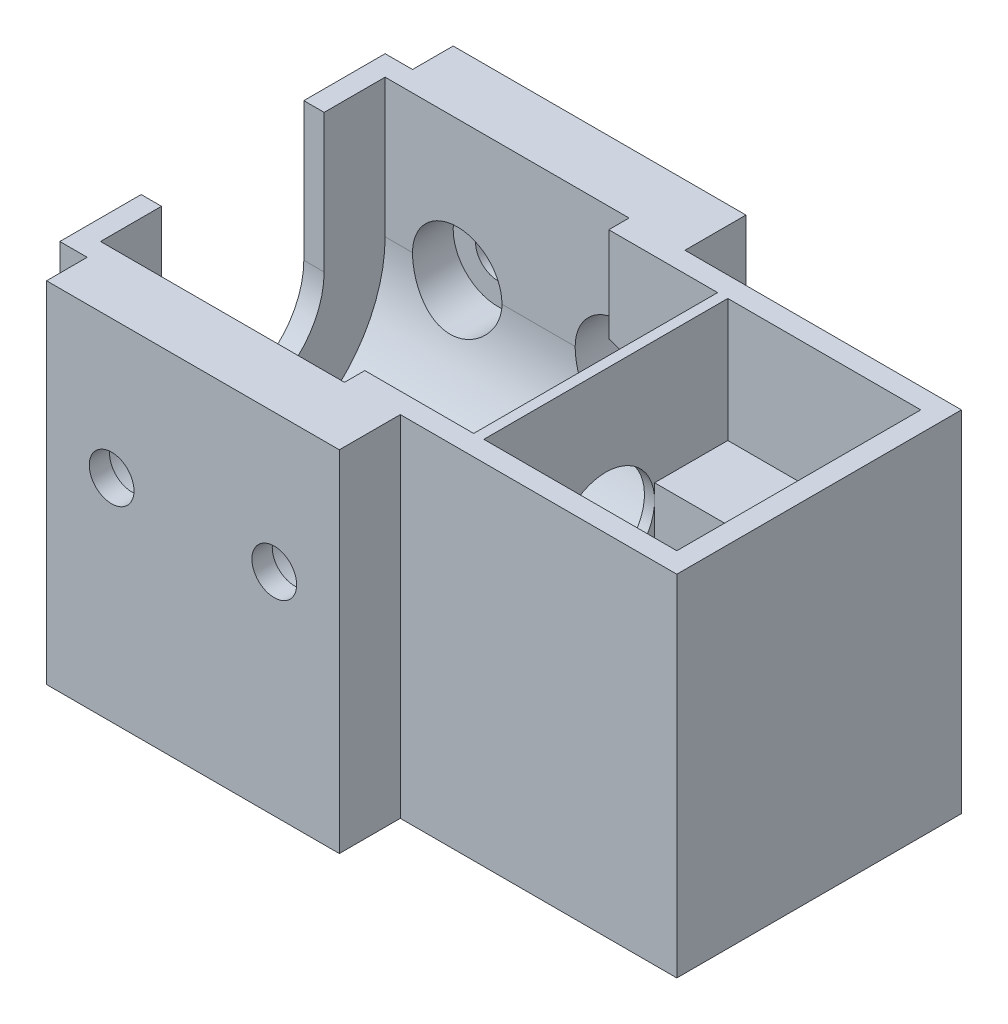
SolidWorks part; units mm, degrees
ref_plane "Front Plane" through (0, 0, 0) normal (0, 0, 1) x (1, 0, 0)
ref_plane "Top Plane" through (0, 0, 0) normal (0, 1, 0) x (1, 0, 0)
ref_plane "Right Plane" through (0, 0, 0) normal (1, 0, 0) x (0, 0, -1)
sketch "Sketch1" plane through (0, 0, 0) normal (0, 0, 1) x (1, 0, 0)
  line L1 (-76.2, -50.8) -> (40.64, -50.8)
  line L2 (-76.2, -50.8) -> (-76.2, 0)
  line L3 (-76.2, 0) -> (40.64, 0)
  line L4 (40.64, -50.8) -> (40.64, 0)
  line L5 (-76.2, -50.8) -> (40.64, 0) construction
  line L6 (-76.2, 0) -> (40.64, -50.8) construction
  point P0 (0, 0)
  dimension "D1" = 116.84
  dimension "D2" = 50.8
  dimension "D3" = 76.2
extrude "Boss-Extrude1" add sketch "Sketch1" along normal mid plane 63.5
sketch "Sketch2" plane through (0, 0, 0) normal (0, 0, 1) x (1, 0, 0)
  line L0 (-152.4829, -25.4) -> (6.8382, -25.4) construction
  line L1 (-49.3609, -3.175) -> (-49.3609, -12.7)
  line L2 (40.64, 0) -> (-76.2, 0) construction
  line L3 (40.64, 0) -> (-76.2, 0) construction
  line L4 (-11.2609, -3.175) -> (-11.2609, -6.35)
  line L5 (-11.2609, -25.4) -> (-11.2609, -3.175) construction
  line L6 (-128.4172, -25.4) -> (-157.8092, -25.4)
  line L7 (6.8382, -25.4) -> (40.64, -25.4)
  line L8 (-607.3619, -25.4) -> (6.8382, -25.4) construction
  line L9 (-49.3609, -3.175) -> (-11.2609, -3.175)
  line L10 (6.8382, -25.4) -> (-128.4172, -25.4)
  line L11 (-11.2609, -6.35) -> (5.7391, -6.35)
  line L12 (5.7391, -6.35) -> (5.7391, -17.78)
  line L13 (5.7391, -17.78) -> (23.7391, -17.78)
  line L14 (-49.3609, -12.7) -> (-220.2024, -12.7)
  line L15 (-220.2024, -12.7) -> (-220.2024, -25.4)
  line L16 (-220.2024, -25.4) -> (-157.8092, -25.4)
  line L17 (23.7391, -17.78) -> (23.7391, -25.4) construction
  line L18 (23.7391, -17.78) -> (40.64, -17.78)
  line L19 (40.64, -50.8) -> (40.64, 0) construction
  line L20 (40.64, -17.78) -> (40.64, -25.4)
  line L21 (-76.2, 0) -> (-76.2, -50.8) construction
  point P23 (-11.2609, -25.4)
  dimension "D1" = 22.225
  dimension "D2" = 38.1
  dimension "D3" = 25.4
  dimension "D4" = 35
  dimension "D5" = 7.62
  dimension "D6" = 3.175
  dimension "D7" = 26.8391
  dimension "D8" = 18
  dimension "D9" = 12.7
revolve "Cut-Revolve1" cut sketch "Sketch2" angle 360 about L0
sketch "Sketch38" plane through (40.64, 0, 0) normal (1, 0, 0) x (0, 0, -1)
  line L1 (-10, -35.4) -> (10, -35.4)
  line L2 (-10, -35.4) -> (-10, -15.4)
  line L3 (-10, -15.4) -> (10, -15.4)
  line L4 (10, -35.4) -> (10, -15.4)
  line L5 (-10, -35.4) -> (10, -15.4) construction
  line L6 (-10, -15.4) -> (10, -35.4) construction
  point P0 (0, -25.4)
  point P1 (0, -25.4)
  dimension "D1" = 20
  dimension "D2" = 20
extrude "Cut-Extrude33" cut sketch "Sketch38" against normal offset from surface (33.3134 mm away) 1.5875 up to face at (5.7391, -44.45, 0)
sketch "Sketch37" plane through (40.64, 0, 0) normal (1, 0, 0) x (0, 0, -1)
  line L0 (31.75, -50.8) -> (31.75, 0) construction
  line L1 (-31.75, 0) -> (31.75, 0)
  line L2 (-31.75, 0) -> (-31.75, -25.4)
  line L3 (-31.75, -25.4) -> (31.75, -25.4)
  line L4 (31.75, 0) -> (31.75, -25.4)
  line L5 (10, -35.4) -> (10, -15.4) construction
  point P7 (0, -25.4)
  point P11 (0, 0)
  point P14 (10, -25.4)
extrude "Cut-Extrude32" cut sketch "Sketch37" against normal through all
sketch "Sketch39" plane through (0, -25.4, 0) normal (0, 1, 0) x (1, 0, 0)
  line L10 (-76.2, 12.7) -> (-49.3609, 12.7)
  line L11 (-49.3609, 12.7) -> (-49.3609, 22.225)
  line L12 (-49.3609, 22.225) -> (-11.2609, 22.225)
  line L13 (-11.2609, 22.225) -> (-11.2609, 19.05)
  line L14 (-11.2609, 19.05) -> (5.7391, 19.05)
  line L15 (5.7391, 19.05) -> (5.7391, 7.62)
  line L16 (5.7391, 19.05) -> (5.7391, 7.62)
  line L17 (40.64, 10) -> (40.64, 31.75)
  line L18 (40.64, 31.75) -> (-76.2, 31.75)
  line L19 (-76.2, 31.75) -> (-76.2, 12.7)
  line L20 (-76.2, 12.7) -> (-49.3609, 12.7)
  line L21 (-49.3609, 12.7) -> (-49.3609, 22.225)
  line L22 (-49.3609, 22.225) -> (-11.2609, 22.225)
  line L23 (-11.2609, 22.225) -> (-11.2609, 19.05)
  line L24 (-11.2609, 19.05) -> (5.7391, 19.05)
  line L25 (7.3266, 10) -> (40.64, 10)
  line L26 (7.3266, 10) -> (40.64, 10)
  line L27 (40.64, 10) -> (40.64, 31.75)
  line L28 (40.64, 31.75) -> (-76.2, 31.75)
  line L29 (-76.2, 31.75) -> (-76.2, 12.7)
  line L30 (-49.3609, -12.7) -> (-76.2, -12.7)
  line L31 (-76.2, -12.7) -> (-76.2, -31.75)
  line L32 (-76.2, -31.75) -> (40.64, -31.75)
  line L33 (40.64, -31.75) -> (40.64, -10)
  line L34 (40.64, -10) -> (7.3266, -10)
  line L35 (40.64, -10) -> (7.3266, -10)
  line L36 (5.7391, -19.05) -> (-11.2609, -19.05)
  line L37 (-11.2609, -19.05) -> (-11.2609, -22.225)
  line L38 (-11.2609, -22.225) -> (-49.3609, -22.225)
  line L39 (-49.3609, -22.225) -> (-49.3609, -12.7)
  line L40 (-49.3609, -12.7) -> (-76.2, -12.7)
  line L41 (-76.2, -12.7) -> (-76.2, -31.75)
  line L42 (-76.2, -31.75) -> (40.64, -31.75)
  line L43 (40.64, -31.75) -> (40.64, -10)
  line L44 (5.7391, -7.62) -> (5.7391, -19.05)
  line L45 (5.7391, -7.62) -> (5.7391, -19.05)
  line L46 (5.7391, -19.05) -> (-11.2609, -19.05)
  line L47 (-11.2609, -19.05) -> (-11.2609, -22.225)
  line L48 (-11.2609, -22.225) -> (-49.3609, -22.225)
  line L49 (-49.3609, -22.225) -> (-49.3609, -12.7)
  line L52 (5.7391, 7.62) -> (7.3266, 7.62)
  line L53 (5.7391, 7.62) -> (7.3266, 7.62)
  line L54 (7.3266, 7.62) -> (7.3266, 10)
  line L55 (7.3266, 7.62) -> (7.3266, 10)
  line L56 (7.3266, -10) -> (7.3266, -7.62)
  line L57 (7.3266, -10) -> (7.3266, -7.62)
  line L58 (7.3266, -7.62) -> (5.7391, -7.62)
  line L59 (7.3266, -7.62) -> (5.7391, -7.62)
  dimension "D1" = 0
  dimension "D2" = 0
extrude "Boss-Extrude5" add sketch "Sketch39" along normal blind 25.4
sketch "Sketch40" plane through (0, 0, 0) normal (0, 1, 0) x (1, 0, 0)
  line L0 (7.3266, 10) -> (40.64, 10) construction
  line L1 (23.7391, 10) -> (40.64, 10)
  line L2 (23.7391, 10) -> (23.7391, -10)
  line L3 (23.7391, -10) -> (40.64, -10)
  line L4 (40.64, 10) -> (40.64, -10)
  line L6 (-11.2609, 22.225) -> (-11.2609, 19.05) construction
  dimension "D1" = 35
extrude "Boss-Extrude6" add sketch "Sketch40" against normal up to next
sketch "Sketch41" plane through (0, 0, 0) normal (0, 1, 0) x (1, 0, 0)
  line L2 (-76.2, 12.7) -> (-76.2, -12.7) construction
  circle A0 centre (-57.15, 0) radius 3.1134
  circle A1 centre (-31.75, 0) radius 3.1134
  circle A2 centre (-6.35, 0) radius 3.1134
  dimension "D1" = 19.05
extrude "Cut-Extrude34" cut sketch "Sketch41" against normal through all
ref_plane "Plane_Mid" through (0, -25.4, 0) normal (0, 1, 0) x (1, 0, 0)
ref_axis "Axis1" through (7.3266, -25.4, 0) along (-1, 0, 0)
sketch "Sketch42" plane through (0, 0, 0) normal (0, 0, 1) x (1, 0, 0)
  line L0 (1.7462, -25.4) -> (-1.7462, -25.4) construction
  line L1 (-76.2, 0) -> (-76.2, -25.4) construction
  circle A0 centre (-38.1, -25.4) radius 3.4925
  circle A1 centre (-12.7, -25.4) radius 3.4925
  dimension "D1" = 6.985
  dimension "D2" = 38.1
extrude "Cut-Extrude35" cut sketch "Sketch42" against normal through all both and the other way through all
sketch "Sketch43" plane through (0, 0, 0) normal (0, 0, 1) x (1, 0, 0)
  circle A0 centre (-38.1, -25.4) radius 6.985
  circle A1 centre (-12.7, -25.4) radius 6.985
  dimension "D1" = 13.97
extrude "Cut-Extrude36" cut sketch "Sketch43" against normal offset from surface (28.575 mm away) 3.175 up to face at (-9.2075, -25.4, -31.75)
extrude "Cut-Extrude37" cut sketch "Sketch43<2>" along normal offset from surface (28.575 mm away) 3.175 up to face at (-9.2075, -25.4, 31.75)
sketch "Sketch43<2>" plane through (0, 0, 0) normal (0, 0, 1) x (1, 0, 0) same geometry as "Sketch43"
sketch "Sketch44" plane through (0, 0, 0) normal (0, 1, 0) x (1, 0, 0)
  line L0 (5.7391, -19.05) -> (-11.2609, -19.05) construction
  line L1 (7.3266, 19.05) -> (23.2391, 19.05)
  line L2 (7.3266, 19.05) -> (7.3266, -19.05)
  line L3 (7.3266, -19.05) -> (23.2391, -19.05)
  line L4 (23.2391, 19.05) -> (23.2391, -19.05)
  line L5 (-11.2609, 19.05) -> (5.7391, 19.05) construction
  line L6 (7.3266, 7.62) -> (7.3266, 10) construction
  line L7 (23.7391, 10) -> (23.7391, -10) construction
  dimension "D1" = 0.5
extrude "Cut-Extrude38" cut sketch "Sketch44" against normal up to surface (35.4 mm away) up to face at (15.5329, -35.4, 0)
sketch "Sketch45" plane through (0, 0, 0) normal (0, 0, 1) x (1, 0, 0)
  line L0 (40.64, 0) -> (-76.2, 0) construction
  line L2 (37.465, 0) -> (23.2391, 0)
  line L4 (37.465, 0) -> (37.465, -15.4)
  line L5 (37.465, -15.4) -> (23.2391, -15.4)
  line L8 (23.2391, 0) -> (23.2391, -15.4)
  line L9 (40.64, -50.8) -> (40.64, 0) construction
  line L10 (23.2391, -35.4) -> (23.2391, 0) construction
  line L11 (-5.715, -25.4) -> (5.7391, -25.4) construction
  dimension "D1" = 3.175
  dimension "D2" = 10
extrude "Cut-Extrude39" cut sketch "Sketch45" against normal up to surface and the other way up to surface up to face at (15.2828, -17.7, -19.05) other way up to face at (15.2828, -17.7, 19.05)
sketch "Sketch46" plane through (0, 0, 0) normal (0, 1, 0) x (1, 0, 0)
  line L0 (-11.2609, 19.05) -> (5.7391, 19.05) construction
  line L1 (40.64, 31.75) -> (-2.54, 31.75)
  line L2 (40.64, 31.75) -> (40.64, 22.225)
  line L3 (40.64, 22.225) -> (-2.54, 22.225)
  line L4 (-2.54, 31.75) -> (-2.54, 22.225)
  line L5 (-76.2, 0) -> (40.64, 0) construction
  line L6 (-76.2, 12.7) -> (-76.2, -12.7) construction
  line L7 (40.64, -31.75) -> (40.64, 31.75) construction
  line L8 (40.64, -31.75) -> (40.64, -22.225)
  line L9 (40.64, -22.225) -> (-2.54, -22.225)
  line L10 (40.64, -31.75) -> (-2.54, -31.75)
  line L11 (-2.54, -31.75) -> (-2.54, -22.225)
  line L12 (-49.3609, 22.225) -> (-11.2609, 22.225) construction
  line L13 (-76.2, 31.75) -> (-48.26, 31.75)
  line L14 (-76.2, 31.75) -> (-76.2, 25.4)
  line L15 (-76.2, 25.4) -> (-48.26, 25.4)
  line L16 (-48.26, 31.75) -> (-48.26, 25.4)
  line L17 (-48.26, -31.75) -> (-48.26, -25.4)
  line L18 (-76.2, -25.4) -> (-48.26, -25.4)
  line L19 (-76.2, -31.75) -> (-76.2, -25.4)
  line L20 (-76.2, -31.75) -> (-48.26, -31.75)
  dimension "D1" = 3.175
  dimension "D2" = 3.175
  dimension "D3" = 3.175
  dimension "D4" = 3.175
extrude "Cut-Extrude40" cut sketch "Sketch46" against normal through all
sketch "Sketch49" plane through (0, 0, 0) normal (0, 1, 0) x (1, 0, 0)
  line L0 (-48.26, -25.4) -> (-76.2, -25.4) construction
  line L1 (-76.2, 25.4) -> (-52.5359, 25.4)
  line L2 (-76.2, 25.4) -> (-76.2, -25.4)
  line L3 (-76.2, -25.4) -> (-52.5359, -25.4)
  line L4 (-52.5359, 25.4) -> (-52.5359, -25.4)
  line L5 (-49.3609, -22.225) -> (-49.3609, 22.225) construction
  dimension "D1" = 3.175
extrude "Cut-Extrude42" cut sketch "Sketch49" against normal through all
sketch "Sketch50" plane through (0, 0, 0) normal (0, 1, 0) x (1, 0, 0)
  line L0 (-2.54, 22.225) -> (40.64, 22.225) construction
  line L1 (22.9851, 20.701) -> (23.2391, 20.701)
  line L2 (22.9851, 20.701) -> (22.9851, 22.225)
  line L3 (22.9851, 22.225) -> (23.2391, 22.225)
  line L4 (23.2391, 20.701) -> (23.2391, 22.225)
  line L5 (23.1121, 22.225) -> (23.1121, 20.701) construction
  line L6 (22.9851, 21.463) -> (23.2391, 21.463) construction
  line L8 (23.2391, 10) -> (23.2391, 19.05) construction
  line L9 (21.4611, 20.701) -> (21.7151, 20.701)
  line L10 (21.7151, 20.701) -> (21.7151, 22.225)
  line L11 (21.4611, 22.225) -> (21.7151, 22.225)
  line L12 (21.4611, 20.701) -> (21.4611, 22.225)
  line L13 (19.9371, 20.701) -> (20.1911, 20.701)
  line L14 (20.1911, 20.701) -> (20.1911, 22.225)
  line L15 (19.9371, 22.225) -> (20.1911, 22.225)
  line L16 (19.9371, 20.701) -> (19.9371, 22.225)
  line L17 (18.4131, 20.701) -> (18.6671, 20.701)
  line L18 (18.6671, 20.701) -> (18.6671, 22.225)
  line L19 (18.4131, 22.225) -> (18.6671, 22.225)
  line L20 (18.4131, 20.701) -> (18.4131, 22.225)
  line L21 (16.8891, 20.701) -> (17.1431, 20.701)
  line L22 (17.1431, 20.701) -> (17.1431, 22.225)
  line L23 (16.8891, 22.225) -> (17.1431, 22.225)
  line L24 (16.8891, 20.701) -> (16.8891, 22.225)
  line L25 (15.3651, 20.701) -> (15.6191, 20.701)
  line L26 (15.6191, 20.701) -> (15.6191, 22.225)
  line L27 (15.3651, 22.225) -> (15.6191, 22.225)
  line L28 (15.3651, 20.701) -> (15.3651, 22.225)
  line L29 (13.8411, 20.701) -> (14.0951, 20.701)
  line L30 (14.0951, 20.701) -> (14.0951, 22.225)
  line L31 (13.8411, 22.225) -> (14.0951, 22.225)
  line L32 (13.8411, 20.701) -> (13.8411, 22.225)
  line L33 (12.3171, 20.701) -> (12.5711, 20.701)
  line L34 (12.5711, 20.701) -> (12.5711, 22.225)
  line L35 (12.3171, 22.225) -> (12.5711, 22.225)
  line L36 (12.3171, 20.701) -> (12.3171, 22.225)
  line L37 (10.7931, 20.701) -> (11.0471, 20.701)
  line L38 (11.0471, 20.701) -> (11.0471, 22.225)
  line L39 (10.7931, 22.225) -> (11.0471, 22.225)
  line L40 (10.7931, 20.701) -> (10.7931, 22.225)
  line L41 (9.2691, 20.701) -> (9.5231, 20.701)
  line L42 (9.5231, 20.701) -> (9.5231, 22.225)
  line L43 (9.2691, 22.225) -> (9.5231, 22.225)
  line L44 (9.2691, 20.701) -> (9.2691, 22.225)
  point P0 (23.1121, 21.463)
  dimension "D1" = 0.254
  dimension "D2" = 1.524
  dimension "D3" = 10
extrude "Cut-Extrude43" cut sketch "Sketch50" against normal blind 2.54
sketch "Sketch52" plane through (23.7391, 0, 0) normal (-1, 0, 0) x (0, 0, 1)
  circle A0 centre (0, -25.4) radius 0.3175
  dimension "D1" = 0.635
extrude "Cut-Extrude45" cut sketch "Sketch52" against normal blind 0.0508
sketch "Sketch53" plane through (23.7391, 0, 0) normal (-1, 0, 0) x (0, 0, 1)
  circle A0 centre (0, -25.4) radius 2
  dimension "D1" = 4
extrude "Cut-Extrude46" cut sketch "Sketch53" against normal blind 0.0254
sketch "Sketch54" plane through (0, -35.4, 0) normal (0, 1, 0) x (1, 0, 0)
  line L0 (23.2391, 10) -> (23.2391, -10)
  line L8 (23.7391, 10) -> (23.2391, 10)
  line L9 (23.2391, 10) -> (23.2391, 19.05)
  line L10 (23.2391, 19.05) -> (7.3266, 19.05)
  line L11 (7.3266, 19.05) -> (7.3266, -19.05)
  line L12 (7.3266, -19.05) -> (23.2391, -19.05)
  line L13 (23.2391, -19.05) -> (23.2391, -10)
  line L14 (23.2391, -10) -> (23.7391, -10)
  line L15 (23.7391, -10) -> (23.7391, 10)
  line L17 (23.2391, 10) -> (23.2391, 19.05)
  line L18 (23.2391, 19.05) -> (7.3266, 19.05)
  line L19 (7.3266, 19.05) -> (7.3266, -19.05)
  line L20 (7.3266, -19.05) -> (23.2391, -19.05)
  line L21 (23.2391, -19.05) -> (23.2391, -10)
  dimension "D1" = 0
extrude "Boss-Extrude7" add sketch "Sketch54" along normal blind 2.54
sketch "Sketch55" plane through (0, -32.86, 0) normal (0, 1, 0) x (1, 0, 0)
  line L0 (23.2391, -19.05) -> (23.2391, -10) construction
  line L1 (23.2391, 10) -> (7.3266, 10)
  line L2 (23.2391, 10) -> (23.2391, 19.05)
  line L3 (23.2391, 19.05) -> (7.3266, 19.05)
  line L4 (7.3266, 10) -> (7.3266, 19.05)
  line L5 (23.2391, 10) -> (7.3266, 19.05) construction
  line L6 (23.2391, 19.05) -> (7.3266, 10) construction
  line L7 (7.3266, -19.05) -> (23.2391, -19.05)
  line L8 (7.3266, -19.05) -> (7.3266, -10)
  line L9 (7.3266, -10) -> (23.2391, -10)
  line L10 (23.2391, -19.05) -> (23.2391, -10)
  line L11 (7.3266, -19.05) -> (23.2391, -10) construction
  line L12 (7.3266, -10) -> (23.2391, -19.05) construction
  point P4 (15.2828, 14.525)
  point P11 (15.2828, -14.525)
extrude "Boss-Extrude8" add sketch "Sketch55" along normal up to surface (17.46 mm away) up to face at (26.9206, -15.4, 0)
sketch "Sketch56" plane through (0, 0, 0) normal (0, 0, 1) x (1, 0, 0)
  line L0 (16.8891, -27.4) -> (16.8891, -32.86) construction
  line L1 (23.7645, -27.4) -> (16.8891, -27.4) construction
  line L2 (23.7645, -23.4) -> (23.7645, -27.4) construction
  line L3 (7.3266, -25.4) -> (5.7391, -25.4) construction
  line L4 (7.3266, -32.86) -> (7.3266, -25.4) construction
  line L5 (12.1079, -30.13) -> (7.3266, -30.13) construction
  line L6 (12.1079, -30.13) -> (16.8891, -30.13) construction
  line L7 (16.8891, -27.4) -> (23.2391, -27.4)
  line L8 (23.2391, -27.4) -> (23.2391, -32.86)
  line L9 (7.3266, -32.86) -> (23.2391, -32.86)
  spline S0 degree 3 poles (7.3266, -32.86) (8.2588, -32.86) (15.2245, -27.986) (15.5713, -27.4) (16.8891, -27.4) knots 0 0 0 0 0.327131 1 1 1 1
  point P6 (16.8891, -30.13)
  dimension "D1" = 2
  dimension "D2" = 6.35
extrude "Boss-Extrude9" add sketch "Sketch56" along normal up to next and the other way up to next
sketch "Sketch57" plane through (0, -15.4, 0) normal (0, 1, 0) x (1, 0, 0)
  line L8 (23.7391, -10) -> (7.3266, -10)
  line L9 (7.3266, -10) -> (7.3266, -19.05)
  line L10 (7.3266, -19.05) -> (37.465, -19.05)
  line L11 (37.465, -19.05) -> (37.465, 19.05)
  line L12 (37.465, 19.05) -> (7.3266, 19.05)
  line L13 (23.7391, -10) -> (7.3266, -10)
  line L14 (7.3266, 19.05) -> (7.3266, 10)
  line L15 (23.7391, 10) -> (23.7391, -10)
  line L16 (7.3266, 19.05) -> (7.3266, 10)
  line L17 (7.3266, -10) -> (7.3266, -19.05)
  line L18 (7.3266, -19.05) -> (37.465, -19.05)
  line L19 (37.465, -19.05) -> (37.465, 19.05)
  line L20 (37.465, 19.05) -> (7.3266, 19.05)
  line L21 (7.3266, 10) -> (23.7391, 10)
  line L22 (7.3266, 10) -> (23.7391, 10)
  line L23 (23.7391, 10) -> (23.7391, -10)
  dimension "D1" = 0
extrude "Cut-Extrude47" cut sketch "Sketch57" against normal blind 7.62
sketch "Sketch58" plane through (0, -50.8, 0) normal (0, -1, 0) x (1, 0, 0)
  line L12 (-48.26, 25.4) -> (-52.5359, 25.4)
  line L13 (-52.5359, 25.4) -> (-52.5359, -25.4)
  line L14 (-52.5359, -25.4) -> (-48.26, -25.4)
  line L15 (-48.26, -25.4) -> (-48.26, -31.75)
  line L16 (-48.26, -31.75) -> (-2.54, -31.75)
  line L17 (-2.54, -31.75) -> (-2.54, -22.225)
  line L18 (-2.54, -22.225) -> (40.64, -22.225)
  line L19 (40.64, -22.225) -> (40.64, 22.225)
  line L20 (40.64, 22.225) -> (-2.54, 22.225)
  line L21 (-2.54, 22.225) -> (-2.54, 31.75)
  line L22 (-2.54, 31.75) -> (-48.26, 31.75)
  line L23 (-48.26, 31.75) -> (-48.26, 25.4)
  line L24 (-48.26, 25.4) -> (-52.5359, 25.4)
  line L25 (-52.5359, 25.4) -> (-52.5359, -25.4)
  line L26 (-52.5359, -25.4) -> (-48.26, -25.4)
  line L27 (-48.26, -25.4) -> (-48.26, -31.75)
  line L28 (-48.26, -31.75) -> (-2.54, -31.75)
  line L29 (-2.54, -31.75) -> (-2.54, -22.225)
  line L30 (-2.54, -22.225) -> (40.64, -22.225)
  line L31 (40.64, -22.225) -> (40.64, 22.225)
  line L32 (40.64, 22.225) -> (-2.54, 22.225)
  line L33 (-2.54, 22.225) -> (-2.54, 31.75)
  line L34 (-2.54, 31.75) -> (-48.26, 31.75)
  line L35 (-48.26, 31.75) -> (-48.26, 25.4)
  circle A0 centre (-31.75, 0) radius 3.1134
  circle A1 centre (-6.35, 0) radius 3.1134
  circle A2 centre (-6.35, 0) radius 3.1134 construction
  circle A3 centre (-31.75, 0) radius 3.1134 construction
  dimension "D1" = 0
extrude "Boss-Extrude10" add sketch "Sketch58" along normal blind 7.62
sketch "Sketch59" plane through (0, -35.4, 0) normal (0, 1, 0) x (1, 0, 0)
  line L4 (23.2391, 10) -> (23.2391, -10)
  line L5 (23.2391, -10) -> (23.7391, -10)
  line L6 (23.7391, -10) -> (23.7391, 10)
  line L7 (23.7391, 10) -> (23.2391, 10)
  line L8 (23.2391, 10) -> (23.2391, -10)
  line L9 (23.2391, -10) -> (23.7391, -10)
  line L10 (23.7391, -10) -> (23.7391, 10)
  line L11 (23.7391, 10) -> (23.2391, 10)
  dimension "D1" = 0
extrude "Cut-Extrude48" cut sketch "Sketch59" against normal blind 7.62
sketch "Sketch51" plane through (0, -23.02, 0) normal (0, 1, 0) x (1, 0, 0)
  line L0 (25.098, 0.254) -> (26.1082, 0.254)
  line L1 (24.59, 2.54) -> (25.098, 2.54)
  line L2 (24.59, 2.54) -> (24.59, 0.254)
  line L3 (24.59, -2.54) -> (25.098, -2.54)
  line L4 (25.098, 2.54) -> (25.098, 0.254)
  line L5 (29.6527, -0.254) -> (30.6629, -0.254)
  line L6 (25.098, -0.254) -> (25.098, -2.54)
  line L7 (26.6162, 2.54) -> (26.6162, 0.254)
  line L8 (26.1082, 2.54) -> (26.6162, 2.54)
  line L9 (26.1082, 2.54) -> (26.1082, 0.254)
  line L10 (26.1082, -2.54) -> (26.6162, -2.54)
  line L11 (28.1344, 2.54) -> (28.1344, 0.254)
  line L12 (27.6264, 2.54) -> (28.1344, 2.54)
  line L13 (27.6264, 2.54) -> (27.6264, 0.254)
  line L14 (27.6264, -2.54) -> (28.1344, -2.54)
  line L15 (29.6527, 2.54) -> (29.6527, 0.254)
  line L16 (29.1447, 2.54) -> (29.6527, 2.54)
  line L17 (29.1447, 2.54) -> (29.1447, 0.254)
  line L18 (29.1447, -2.54) -> (29.6527, -2.54)
  line L19 (31.1709, 2.54) -> (31.1709, 0.254)
  line L20 (30.6629, 2.54) -> (31.1709, 2.54)
  line L21 (30.6629, 2.54) -> (30.6629, 0.254)
  line L22 (30.6629, -2.54) -> (31.1709, -2.54)
  line L23 (32.6891, 2.54) -> (32.6891, 0.254)
  line L24 (32.1811, 2.54) -> (32.6891, 2.54)
  line L25 (32.1811, 2.54) -> (32.1811, 0.254)
  line L26 (32.1811, -2.54) -> (32.6891, -2.54)
  line L27 (34.2073, 2.54) -> (34.2073, 0.254)
  line L28 (33.6993, 2.54) -> (34.2073, 2.54)
  line L29 (33.6993, 2.54) -> (33.6993, 0.254)
  line L30 (33.6993, -2.54) -> (34.2073, -2.54)
  line L31 (35.7255, 2.54) -> (35.7255, 0.254)
  line L32 (35.2175, 2.54) -> (35.7255, 2.54)
  line L33 (35.2175, 2.54) -> (35.2175, 0.254)
  line L34 (35.2175, -2.54) -> (35.7255, -2.54)
  line L35 (35.258, 2.5876) -> (24.581, 2.5876) construction
  line L36 (23.32, 11.7754) -> (37.465, 11.7754) construction
  line L37 (25.098, -0.254) -> (26.1082, -0.254)
  line L38 (23.7391, 10) -> (23.7391, -10) construction
  line L39 (37.465, -19.05) -> (37.465, 19.05) construction
  line L40 (23.7391, 0.254) -> (24.59, 0.254)
  line L41 (23.7391, 0.254) -> (23.7391, -0.254)
  line L42 (23.7391, -0.254) -> (24.59, -0.254)
  line L43 (37.465, 0.254) -> (37.465, -0.254)
  line L44 (31.1709, 0.254) -> (32.1811, 0.254)
  line L46 (24.59, -0.254) -> (24.59, -2.54)
  line L47 (26.1082, -0.254) -> (26.1082, -2.54)
  line L48 (26.6162, 0.254) -> (27.6264, 0.254)
  line L49 (26.6162, -0.254) -> (26.6162, -2.54)
  line L51 (26.6162, -0.254) -> (27.6264, -0.254)
  line L52 (27.6264, -0.254) -> (27.6264, -2.54)
  line L53 (28.1344, 0.254) -> (29.1447, 0.254)
  line L54 (28.1344, -0.254) -> (29.1447, -0.254)
  line L55 (28.1344, -0.254) -> (28.1344, -2.54)
  line L56 (29.1447, -0.254) -> (29.1447, -2.54)
  line L57 (29.6527, 0.254) -> (30.6629, 0.254)
  line L58 (31.1709, -0.254) -> (32.1811, -0.254)
  line L61 (29.6527, -0.254) -> (29.6527, -2.54)
  line L62 (30.6629, -0.254) -> (30.6629, -2.54)
  line L63 (31.1709, -0.254) -> (31.1709, -2.54)
  line L64 (32.1811, -0.254) -> (32.1811, -2.54)
  line L65 (32.6891, 0.254) -> (33.6993, 0.254)
  line L66 (32.6891, -0.254) -> (33.6993, -0.254)
  line L67 (32.6891, -0.254) -> (32.6891, -2.54)
  line L68 (33.6993, -0.254) -> (33.6993, -2.54)
  line L69 (34.2073, 0.254) -> (35.2175, 0.254)
  line L70 (34.2073, -0.254) -> (35.2175, -0.254)
  line L71 (34.2073, -0.254) -> (34.2073, -2.54)
  line L72 (35.2175, -0.254) -> (35.2175, -2.54)
  line L73 (35.7255, -0.254) -> (35.7255, -2.54)
  line L74 (35.7255, 0.254) -> (37.465, 0.254)
  line L75 (35.7255, -0.254) -> (37.465, -0.254)
  text T1 "<b>v7</b>"
  point P0 (24.717, 0)
  point P51 (30.3925, 0)
  point P52 (23.7391, 0)
  dimension "D1" = 0.508
  dimension "D2" = 5.08
  dimension "D3" = 1.5182
  dimension "D5" = 0.8419
  dimension "D6" = 0.508
  dimension "D4" = 8
extrude "Cut-Extrude44" cut sketch "Sketch51" against normal blind 0.635
sketch "Sketch60" plane through (0, 0, 0) normal (0, 1, 0) x (1, 0, 0)
  line L1 (-60.6783, -40.5295) -> (60.6783, -40.5295)
  line L2 (-60.6783, -40.5295) -> (-60.6783, 40.5295)
  line L3 (-60.6783, 40.5295) -> (60.6783, 40.5295)
  line L4 (60.6783, -40.5295) -> (60.6783, 40.5295)
  line L5 (0, 40.5295) -> (0, -40.5295) construction
  line L6 (-60.6783, 0) -> (60.6783, 0) construction
  point P0 (0, 0)
extrude "Cut-Extrude49" cut sketch "Sketch60" against normal blind 10.16
ref_plane "Plane_Bottom" through (0, -47.625, 0) normal (0, 1, 0) x (1, 0, 0)
ref_plane "Plane_Top" through (0, -3.81, 0) normal (0, 1, 0) x (1, 0, 0)
sketch "Sketch61" plane through (5.7391, 0, 0) normal (-1, 0, 0) x (0, 0, 1)
  circle A0 centre (0, -25.4) radius 7.62
  circle A1 centre (0, -25.4) radius 8.9762
extrude "Boss-Extrude11" add sketch "Sketch61" against normal up to surface (1.5875 mm away) up to face at (7.3266, -21.9643, -11.7357)
sketch "Sketch62" plane through (0, -10.16, 0) normal (0, 1, 0) x (1, 0, 0)
  line L1 (7.3266, 7.62) -> (5.7391, 7.62)
  line L2 (7.3266, 7.62) -> (7.3266, -7.62)
  line L3 (7.3266, -7.62) -> (5.7391, -7.62)
  line L4 (5.7391, 7.62) -> (5.7391, -7.62)
  line L5 (7.3266, 7.62) -> (5.7391, -7.62) construction
  line L6 (7.3266, -7.62) -> (5.7391, 7.62) construction
  point P4 (6.5328, 0)
extrude "Boss-Extrude12" add sketch "Sketch62" against normal up to next
sketch "Sketch64" plane through (0, -10.16, 0) normal (0, 1, 0) x (1, 0, 0)
  line L25 (37.465, 19.05) -> (7.3266, 19.05)
  line L26 (37.465, 19.05) -> (37.465, -19.05)
  line L27 (37.465, -19.05) -> (7.3266, -19.05)
  line L28 (7.3266, 19.05) -> (7.3266, -19.05)
  line L29 (37.465, 19.05) -> (7.3266, -19.05) construction
  line L30 (37.465, -19.05) -> (7.3266, 19.05) construction
  line L48 (-11.2609, 19.05) -> (5.7391, 19.05)
  line L49 (5.7391, 19.05) -> (5.7391, -19.05)
  line L50 (5.7391, -19.05) -> (-11.2609, -19.05)
  line L51 (-11.2609, -19.05) -> (-11.2609, -22.225)
  line L52 (-11.2609, -22.225) -> (-49.3609, -22.225)
  line L53 (-49.3609, -22.225) -> (-49.3609, -12.7)
  line L54 (-49.3609, -12.7) -> (-52.5359, -12.7)
  line L55 (-52.5359, -12.7) -> (-52.5359, -25.4)
  line L56 (-52.5359, -25.4) -> (-48.26, -25.4)
  line L57 (-48.26, -25.4) -> (-48.26, -31.75)
  line L58 (-48.26, -31.75) -> (-2.54, -31.75)
  line L59 (-2.54, -31.75) -> (-2.54, -22.225)
  line L60 (-2.54, -22.225) -> (40.64, -22.225)
  line L61 (40.64, -22.225) -> (40.64, 22.225)
  line L62 (40.64, 22.225) -> (-2.54, 22.225)
  line L63 (-2.54, 22.225) -> (-2.54, 31.75)
  line L64 (-2.54, 31.75) -> (-48.26, 31.75)
  line L65 (-48.26, 31.75) -> (-48.26, 25.4)
  line L66 (-48.26, 25.4) -> (-52.5359, 25.4)
  line L67 (-52.5359, 25.4) -> (-52.5359, 12.7)
  line L68 (-52.5359, 12.7) -> (-49.3609, 12.7)
  line L69 (-49.3609, 12.7) -> (-49.3609, 22.225)
  line L70 (-49.3609, 22.225) -> (-11.2609, 22.225)
  line L71 (-11.2609, 22.225) -> (-11.2609, 19.05)
  line L72 (-11.2609, 19.05) -> (5.7391, 19.05)
  line L73 (5.7391, 19.05) -> (5.7391, -19.05)
  line L74 (5.7391, -19.05) -> (-11.2609, -19.05)
  line L75 (-11.2609, -19.05) -> (-11.2609, -22.225)
  line L76 (-11.2609, -22.225) -> (-49.3609, -22.225)
  line L77 (-49.3609, -22.225) -> (-49.3609, -12.7)
  line L78 (-49.3609, -12.7) -> (-52.5359, -12.7)
  line L79 (-52.5359, -12.7) -> (-52.5359, -25.4)
  line L80 (-52.5359, -25.4) -> (-48.26, -25.4)
  line L81 (-48.26, -25.4) -> (-48.26, -31.75)
  line L82 (-48.26, -31.75) -> (-2.54, -31.75)
  line L83 (-2.54, -31.75) -> (-2.54, -22.225)
  line L84 (-2.54, -22.225) -> (40.64, -22.225)
  line L85 (40.64, -22.225) -> (40.64, 22.225)
  line L86 (40.64, 22.225) -> (-2.54, 22.225)
  line L87 (-2.54, 22.225) -> (-2.54, 31.75)
  line L88 (-2.54, 31.75) -> (-48.26, 31.75)
  line L89 (-48.26, 31.75) -> (-48.26, 25.4)
  line L90 (-48.26, 25.4) -> (-52.5359, 25.4)
  line L91 (-52.5359, 25.4) -> (-52.5359, 12.7)
  line L92 (-52.5359, 12.7) -> (-49.3609, 12.7)
  line L93 (-49.3609, 12.7) -> (-49.3609, 22.225)
  line L94 (-49.3609, 22.225) -> (-11.2609, 22.225)
  line L95 (-11.2609, 22.225) -> (-11.2609, 19.05)
  point P28 (22.3958, 0)
  dimension "D1" = 0
extrude "Boss-Extrude14" add sketch "Sketch64" along normal up to surface (6.35 mm away) up to plane "Plane_Top"
sketch "Sketch65" plane through (7.3266, 0, 0) normal (1, 0, 0) x (0, 0, -1)
  line L0 (-10, -23.02) -> (-7.62, -23.02)
  line L1 (10, -23.02) -> (7.62, -23.02)
  line L2 (-7.62, -32.86) -> (-7.62, -23.02)
  line L3 (7.62, -32.86) -> (7.62, -23.02)
  line L6 (-10, -23.02) -> (-10, -32.86)
  line L7 (-10, -32.86) -> (-7.62, -32.86)
  line L8 (7.62, -32.86) -> (10, -32.86)
  line L28 (10, -32.86) -> (10, -23.02)
  point P12 (8.81, -23.02)
extrude "Boss-Extrude16" add sketch "Sketch65" along normal up to next
sketch "Sketch66" plane through (0, -23.02, 0) normal (0, 1, 0) x (1, 0, 0)
  line L1 (23.7391, 10) -> (23.2391, 10)
  line L2 (23.7391, 10) -> (23.7391, -10)
  line L3 (23.7391, -10) -> (23.2391, -10)
  line L4 (23.2391, 10) -> (23.2391, -10)
  line L5 (23.7391, 10) -> (23.2391, -10) construction
  line L6 (23.7391, -10) -> (23.2391, 10) construction
  line L7 (23.2391, 7.62) -> (23.2391, -7.62) construction
  line L9 (7.3266, 0) -> (5.7391, 0) construction
  line L10 (23.7391, -0.254) -> (23.7391, -7.62) construction
  point P4 (23.4891, 0)
  dimension "D1" = 20
extrude "Cut-Extrude50" cut sketch "Sketch66" against normal up to surface (20 mm away) up to face at (23.4891, -43.02, 0)
